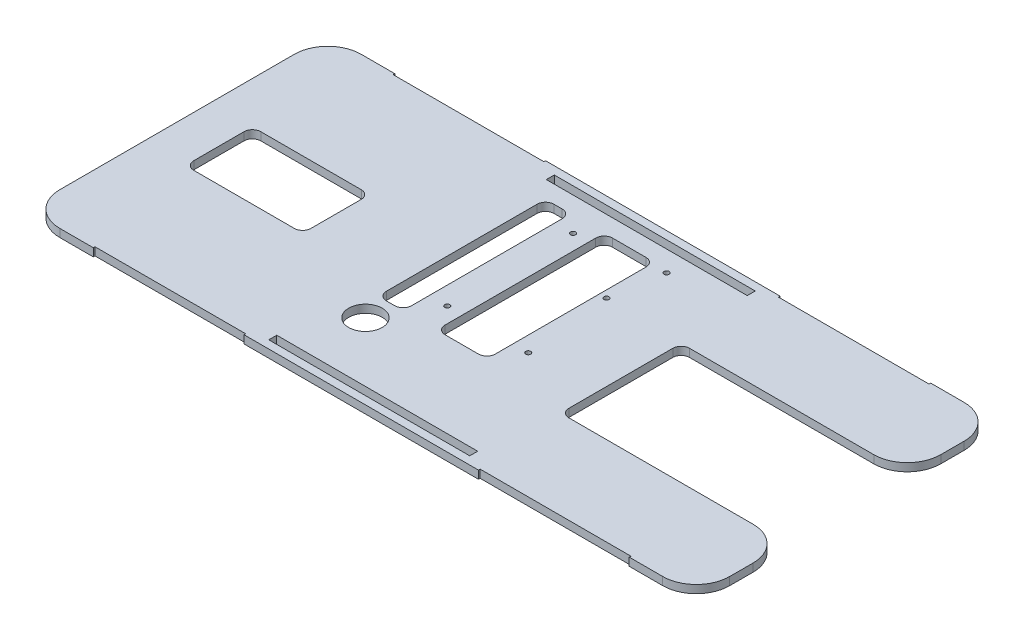
SolidWorks part; units mm, degrees
material "Teak"
ref_plane "Front Plane" through (0, 0, 0) normal (0, 0, 1) x (1, 0, 0)
ref_plane "Top Plane" through (0, 0, 0) normal (0, 1, 0) x (1, 0, 0)
ref_plane "Right Plane" through (0, 0, 0) normal (1, 0, 0) x (0, 0, -1)
sketch "Sketch1" plane through (0, 0, 0) normal (0, 1, 0) x (1, 0, 0)
  line L0 (-160, 89) -> (-160, -89) construction
  line L1 (-200, 90) -> (-160, 90)
  line L2 (-200, 90) -> (-200, -90)
  line L3 (-200, -90) -> (-160, -90)
  line L4 (200, 90) -> (200, -90)
  line L6 (-160, 90) -> (-160, 89)
  line L7 (-160, 89) -> (-70, 89)
  line L8 (-70, 90) -> (-70, 89)
  line L10 (-160, -90) -> (-160, -89)
  line L11 (-160, -89) -> (-70, -89)
  line L12 (-70, -90) -> (-70, -89)
  line L14 (70, -90) -> (70, -89)
  line L15 (70, -89) -> (160, -89)
  line L16 (160, -90) -> (160, -89)
  line L18 (70, 90) -> (70, 89)
  line L19 (70, 89) -> (160, 89)
  line L20 (160, 90) -> (160, 89)
  line L21 (-70, 89) -> (-70, -89) construction
  line L22 (70, -89) -> (-70, -89) construction
  line L23 (-70, 89) -> (70, 89) construction
  line L24 (70, -89) -> (70, 89) construction
  line L25 (-70, 90) -> (70, 90)
  line L26 (-70, -90) -> (70, -90)
  line L27 (160, -90) -> (200, -90)
  line L28 (160, 90) -> (200, 90)
  point P22 (200, 0)
  point P23 (-70, 0)
  point P24 (0, -89)
  dimension "D1" = 90
  dimension "D2" = 1
  dimension "D3" = 400
  dimension "D4" = 40
  dimension "D5" = 180
extrude "Boss-Extrude1" add sketch "Sketch1" along normal mid plane 4.7625
sketch "Sketch2" plane through (0, 2.3813, 0) normal (0, 1, 0) x (1, 0, 0)
  line L0 (200, -90) -> (200, 90) construction
  line L1 (200, 36) -> (65, 36)
  line L2 (200, 36) -> (200, -36)
  line L3 (200, -36) -> (65, -36)
  line L4 (65, 36) -> (65, -36)
  point P6 (65, 0)
  dimension "D1" = 72
  dimension "D2" = 135
extrude "Cut-Extrude1" cut sketch "Sketch2" against normal blind 10
sketch "Sketch3" plane through (0, 2.3813, 0) normal (0, 1, 0) x (1, 0, 0)
  line L0 (70, 90) -> (-70, 90) construction
  line L1 (-35, 70) -> (-50, 70)
  line L2 (-35, 70) -> (-35, -30)
  line L3 (-35, -30) -> (-50, -30)
  line L4 (-50, 70) -> (-50, -30)
  line L6 (-200, 90) -> (-200, -90) construction
  line L7 (-175, 20) -> (-105, 20)
  line L8 (-175, 20) -> (-175, -20)
  line L9 (-175, -20) -> (-105, -20)
  line L10 (-105, 20) -> (-105, -20)
  line L12 (-15, 70) -> (15, 70)
  line L13 (-15, 70) -> (-15, -30)
  line L14 (-15, -30) -> (15, -30)
  line L15 (15, 70) -> (15, -30)
  circle A0 centre (-42.5, -45) radius 10
  point P12 (-175, 0)
  point P20 (0, -30)
  point P24 (0, 0)
  point P25 (-42.5, -30)
  dimension "D11" = 20
  dimension "D1" = 100
  dimension "D2" = 15
  dimension "D3" = 20
  dimension "D4" = 20
  dimension "D5" = 70
  dimension "D6" = 40
  dimension "D7" = 25
  dimension "D8" = 30
  dimension "D9" = 100
  dimension "D10" = 20
  dimension "D12" = 15
extrude "Cut-Extrude2" cut sketch "Sketch3" against normal blind 10
sketch "Sketch4" plane through (0, 2.3813, 0) normal (0, 1, 0) x (1, 0, 0)
  circle A0 centre (24.1681, -14.4776) radius 1.5
  circle A1 centre (-24.1681, -14.4776) radius 1.5
  circle A2 centre (-24.1681, 60.6556) radius 1.5
  circle A3 centre (24.1681, 68.1486) radius 1.5
  circle A4 centre (19.2896, 37.1479) radius 1.5
  dimension "D1" = 3
  dimension "D2" = 3
extrude "Cut-Extrude3" cut sketch "Sketch4" against normal blind 10
sketch "Sketch5" plane through (0, 2.3813, 0) normal (0, 1, 0) x (1, 0, 0)
  line L0 (70, 90) -> (-70, 90) construction
  line L1 (-60, 85.2375) -> (60, 85.2375)
  line L2 (-60, 85.2375) -> (-60, 80.475)
  line L3 (-60, 80.475) -> (60, 80.475)
  line L4 (60, 85.2375) -> (60, 80.475)
  line L5 (-70, -90) -> (70, -90) construction
  line L6 (-60, -80.475) -> (60, -80.475)
  line L7 (-60, -80.475) -> (-60, -85.2375)
  line L8 (-60, -85.2375) -> (60, -85.2375)
  line L9 (60, -80.475) -> (60, -85.2375)
  point P4 (0, 80.475)
  dimension "D1" = 4.7625
  dimension "D2" = 120
  dimension "D3" = 4.7625
  dimension "D4" = 4.7625
extrude "Cut-Extrude4" cut sketch "Sketch5" against normal blind 10
fillet "Fillet1" radius 20 4 edges at (-200, 0, -90) (-200, 0, 90) (200, 0, -90) (200, 0, 90)
fillet "Fillet2" radius 20 2 edges at (200, 0, 36) (200, 0, -36)
fillet "Fillet3" radius 5 14 edges at (65, 0, -36) (65, 0, 36) (15, 0, -70) (15, 0, 30) (-15, 0, 30) (-15, 0, -70) (-35, 0, -70) (-50, 0, -70) (-35, 0, 30) (-50, 0, 30) (-105, 0, 20) (-175, 0, 20) (-175, 0, -20) (-105, 0, -20)
